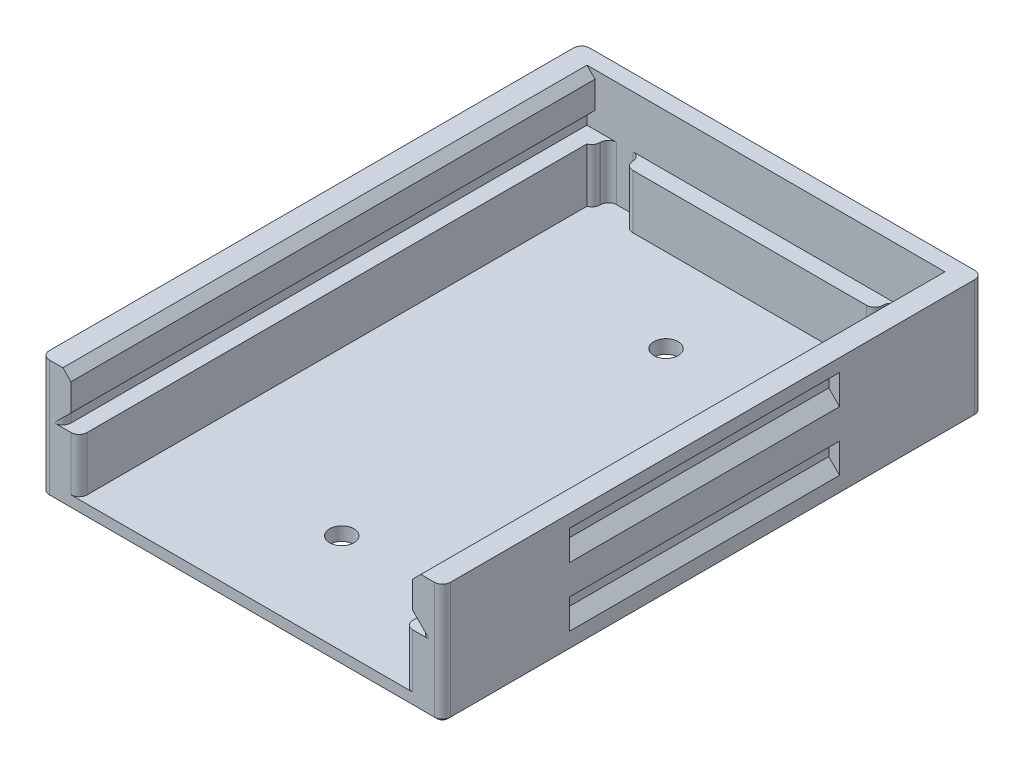
SolidWorks part; units mm, degrees
ref_plane "Front Plane" through (0, 0, 0) normal (0, 0, 1) x (1, 0, 0)
ref_plane "Top Plane" through (0, 0, 0) normal (0, 1, 0) x (1, 0, 0)
ref_plane "Right Plane" through (0, 0, 0) normal (1, 0, 0) x (0, 0, -1)
sketch "Sketch1" plane through (0, 0, 0) normal (0, 1, 0) x (1, 0, 0)
  line L1 (33.125, 48.5) -> (-33.125, 48.5)
  line L2 (33.125, 48.5) -> (33.125, -48.5)
  line L3 (33.125, -48.5) -> (-33.125, -48.5)
  line L4 (-33.125, 48.5) -> (-33.125, -48.5)
  line L5 (33.125, 48.5) -> (-33.125, -48.5) construction
  line L6 (33.125, -48.5) -> (-33.125, 48.5) construction
  point P0 (0, 0)
  dimension "D1" = 97
  dimension "D2" = 66.25
extrude "Boss-Extrude1" add sketch "Sketch1" along normal blind 2.5
sketch "Sketch2" plane through (0, 0, 48.5) normal (0, 0, 1) x (1, 0, 0)
  line L0 (0, 0) -> (0, 48.759) construction
  line L1 (30.125, 2.5) -> (30.125, 12.5)
  line L3 (30.125, 12.5) -> (33.125, 12.5)
  line L4 (33.125, 12.5) -> (33.125, 14.12)
  line L5 (33.125, 14.12) -> (31.625, 15.62)
  line L6 (31.625, 15.62) -> (31.625, 20.62)
  line L7 (31.625, 20.62) -> (33.125, 22.12)
  line L8 (33.125, 22.12) -> (37.125, 22.12)
  line L10 (37.125, 22.12) -> (37.125, 0)
  line L11 (37.125, 0) -> (30.125, 0)
  line L13 (30.125, 0) -> (30.125, 2.5)
  line L15 (-31.625, 20.62) -> (-33.125, 22.12)
  line L16 (-31.625, 15.62) -> (-31.625, 20.62)
  line L17 (-33.125, 14.12) -> (-31.625, 15.62)
  line L18 (-33.125, 12.5) -> (-33.125, 14.12)
  line L19 (-30.125, 12.5) -> (-33.125, 12.5)
  line L20 (-30.125, 2.5) -> (-30.125, 12.5)
  line L21 (-33.125, 22.12) -> (-37.125, 22.12)
  line L22 (-37.125, 22.12) -> (-37.125, 0)
  line L23 (-30.125, 2.5) -> (-30.125, 0)
  line L24 (-33.125, 2.5) -> (33.125, 2.5) construction
  line L25 (-33.125, 0) -> (33.125, 0) construction
  line L26 (33.125, 2.5) -> (33.125, 0) construction
  line L27 (-30.125, 0) -> (-37.125, 0)
  dimension "D2" = 10
  dimension "D3" = 3
  dimension "D4" = 1.62
  dimension "D5" = 45
  dimension "D6" = 1.5
  dimension "D7" = 4
  dimension "D8" = 8
  dimension "D10" = 4
extrude "Boss-Extrude2" add sketch "Sketch2" against normal up to surface (97 mm away) up to face at (0, 1.25, -48.5)
sketch "Sketch3" plane through (0, 2.5, 0) normal (0, 1, 0) x (1, 0, 0)
  line L0 (-23.125, 48.5) -> (-23.125, 45.5)
  line L1 (0, 48.5) -> (0, 33.3305) construction
  line L2 (30.125, 48.5) -> (-30.125, 48.5) construction
  line L3 (-23.125, 48.5) -> (0, 48.5)
  line L4 (30.125, 48.5) -> (29.125, 48.5)
  line L5 (30.125, 48.5) -> (30.125, 45.5)
  line L6 (30.125, 45.5) -> (29.125, 45.5)
  line L7 (29.125, 48.5) -> (29.125, 45.5)
  line L8 (23.125, 48.5) -> (0, 48.5)
  line L9 (23.125, 48.5) -> (23.125, 45.5)
  line L10 (23.125, 45.5) -> (-23.125, 45.5)
  line L11 (0, 48.5) -> (0, 45.5) construction
  line L12 (-29.125, 48.5) -> (-29.125, 45.5)
  line L13 (-30.125, 45.5) -> (-29.125, 45.5)
  line L14 (-30.125, 48.5) -> (-30.125, 45.5)
  line L15 (-30.125, 48.5) -> (-29.125, 48.5)
  dimension "D1" = 3
  dimension "D2" = 4
  dimension "D3" = 6
extrude "Boss-Extrude3" add sketch "Sketch3" along normal up to surface (10 mm away) up to face at (31.625, 12.5, 0)
sketch "Sketch4" plane through (0, 0, 0) normal (0, -1, 0) x (1, 0, 0)
  line L1 (37.125, -48.5) -> (-37.125, -48.5)
  line L2 (37.125, -48.5) -> (37.125, -51.5)
  line L3 (37.125, -51.5) -> (-37.125, -51.5)
  line L4 (-37.125, -48.5) -> (-37.125, -51.5)
  dimension "D1" = 3
extrude "Boss-Extrude4" add sketch "Sketch4" against normal up to surface (22.12 mm away) up to face at (35.125, 22.12, 0)
sketch "Sketch6" plane through (0, 2.5, 0) normal (0, 1, 0) x (1, 0, 0)
  line L0 (0, 30) -> (0, -30) construction
  circle A0 centre (0, 30) radius 2.25
  circle A1 centre (0, -30) radius 2.25
  dimension "D2" = 4.5
  dimension "D1" = 60
extrude "Cut-Extrude1" cut sketch "Sketch6" against normal through all
fillet "Fillet1" radius 1.5 16 edges at (-33.125, 13.31, 48.5) (33.125, 13.31, 48.5) (-30.125, 7.5, 48.5) (30.125, 7.5, 48.5) (29.125, 7.5, -48.5) (23.125, 7.5, -48.5) (-23.125, 7.5, -48.5) (-29.125, 7.5, -48.5) (-23.125, 7.5, -45.5) (23.125, 7.5, -45.5) (29.125, 7.5, -45.5) (-29.125, 7.5, -45.5) (37.125, 11.06, 48.5) (-37.125, 11.06, 48.5) (-37.125, 11.06, -51.5) (37.125, 11.06, -51.5)
sketch "Sketch7" plane through (0, 0, 0) normal (0, 0, 1) x (1, 0, 0)
  line L0 (0, 0) -> (0, 31.0233) construction
  line L1 (-37.125, 8.75) -> (-35.125, 6.75)
  line L2 (-37.125, 0) -> (-37.125, 22.12) construction
  line L3 (-35.125, 6.75) -> (-35.125, 5.25)
  line L4 (-35.125, 5.25) -> (-37.125, 3.25)
  line L5 (-37.125, 8.75) -> (-37.125, 3.25)
  line L6 (-35.625, 0) -> (35.625, 0) construction
  line L7 (-37.125, 19.75) -> (-35.125, 17.75)
  line L8 (-35.125, 17.75) -> (-35.125, 16.25)
  line L9 (-35.125, 16.25) -> (-37.125, 14.25)
  line L10 (-37.125, 19.75) -> (-37.125, 14.25)
  line L11 (37.125, 19.75) -> (37.125, 14.25)
  line L12 (35.125, 16.25) -> (37.125, 14.25)
  line L13 (35.125, 17.75) -> (35.125, 16.25)
  line L14 (37.125, 19.75) -> (35.125, 17.75)
  line L15 (37.125, 8.75) -> (37.125, 3.25)
  line L16 (35.125, 5.25) -> (37.125, 3.25)
  line L17 (35.125, 6.75) -> (35.125, 5.25)
  line L18 (37.125, 8.75) -> (35.125, 6.75)
  point P7 (-35.125, 6)
  dimension "D1" = 45
  dimension "D2" = 2
  dimension "D3" = 5.5
  dimension "D4" = 6
  dimension "D6" = 11
  dimension "D5" = 2
extrude "Cut-Extrude2" cut sketch "Sketch7" against normal mid plane 50
chamfer "Chamfer1" distance 0.5 angle 45 8 edges at (37.125, 0, -1.5) (36.6857, 0, -51.0607) (36.6857, 0, 48.0607) (0, 0, -51.5) (0, 0, 48.5) (-36.6857, 0, -51.0607) (-36.6857, 0, 48.0607) (-37.125, 0, -1.5)
